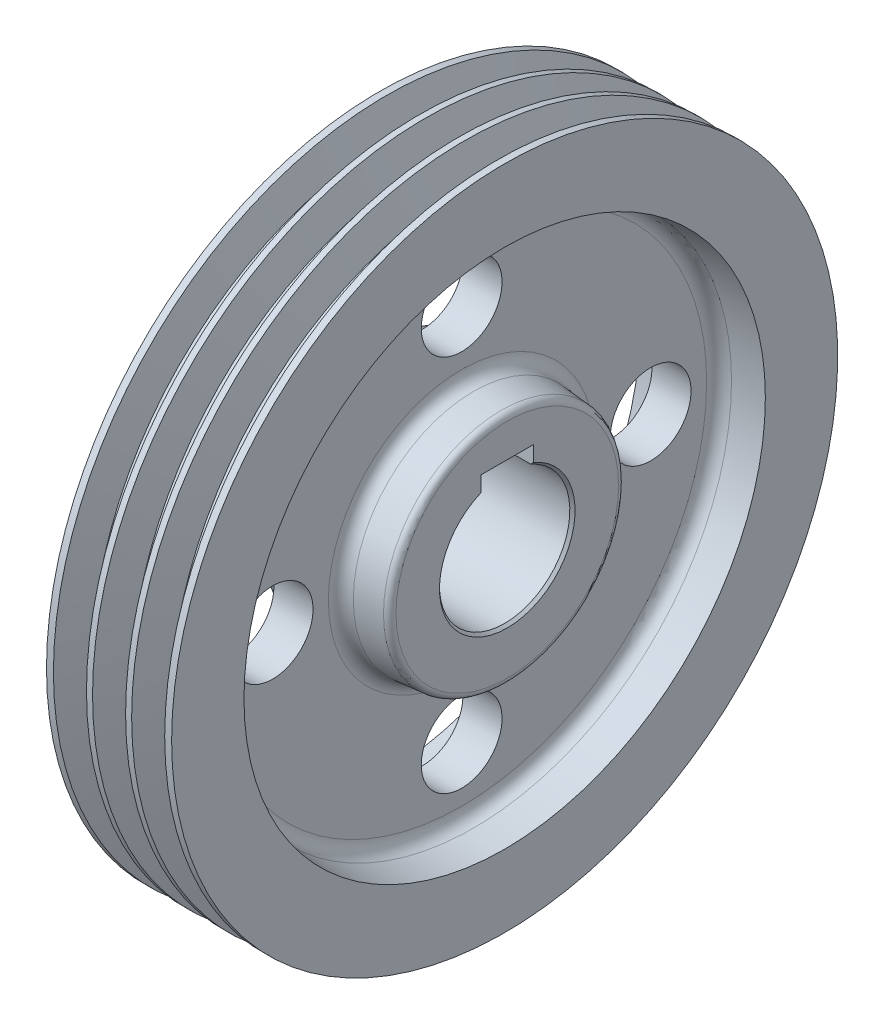
SolidWorks part; units mm, degrees
ref_plane "前视基准面" through (0, 0, 0) normal (0, 0, 1) x (1, 0, 0)
ref_plane "上视基准面" through (0, 0, 0) normal (0, 1, 0) x (1, 0, 0)
ref_plane "右视基准面" through (0, 0, 0) normal (1, 0, 0) x (0, 0, -1)
sketch "草图1" plane through (0, 0, 0) normal (0, 0, 1) x (1, 0, 0)
  line L0 (0, 0) -> (64.8368, 0) construction
  line L1 (-1, 25) -> (-1, 45)
  line L2 (0, 127.75) -> (48, 127.75)
  line L3 (48, 127.75) -> (48, 100)
  line L4 (-1, 45) -> (-30, 45) construction
  line L5 (16.5, 46.5311) -> (16.5, 98.5564)
  line L6 (49, 25) -> (-1, 25)
  line L7 (2.6592, 127.75) -> (6.1599, 116.3) construction
  line L8 (6.1599, 116.3) -> (11.8401, 116.3) construction
  line L9 (11.8401, 116.3) -> (15.3408, 127.75) construction
  line L10 (0, 125) -> (48, 125) construction
  line L11 (9, 116.3) -> (9, 25) construction
  line L12 (44, 100) -> (0, 100) construction
  line L13 (48, 100) -> (79, 100) construction
  line L14 (31.5, 98.5564) -> (31.5, 46.5311)
  line L15 (5, 45) -> (49, 45) construction
  line L16 (24, 25) -> (24, 127.75) construction
  line L17 (49, 45) -> (49, 25)
  line L18 (0, 100) -> (0, 127.75)
  line L19 (16.5, 88) -> (31.5, 88) construction
  line L20 (16.5, 57) -> (31.5, 57) construction
  line L21 (48, 100) -> (48, 88) construction
  line L22 (48, 88) -> (31.5, 88) construction
  line L23 (31.5, 57) -> (49, 57) construction
  line L24 (49, 57) -> (49, 45) construction
  line L25 (31.5, 98.5564) -> (48, 100)
  line L26 (16.5, 98.5564) -> (0, 100)
  line L27 (16.5, 46.5311) -> (-1, 45)
  line L28 (31.5, 46.5311) -> (49, 45)
  point P17 (3.5, 125)
  point P18 (14.5, 125)
  dimension "d2" = 200
  dimension "L" = 50
  dimension "B" = 48
  dimension "d" = 50
  dimension "d1" = 90
  dimension "D3" = 5
  dimension "D4" = 5
  dimension "dd" = 250
  dimension "f" = 9
  dimension "槽轮角" = 34
  dimension "bd" = 11
  dimension "hf" = 8.7
  dimension "ha" = 2.75
  dimension "da" = 255.5
  dimension "S" = 15
  dimension "S2" = 12
revolve "旋转1" add sketch "草图1" angle 360 about L0
sketch "草图2" plane through (0, 0, 0) normal (0, 0, 1) x (1, 0, 0)
  line L0 (11.8401, 116.3) -> (15.3408, 127.75) construction
  line L1 (6.1599, 116.3) -> (11.8401, 116.3) construction
  line L2 (2.6592, 127.75) -> (6.1599, 116.3) construction
  line L3 (11.8401, 116.3) -> (15.3408, 127.75)
  line L4 (6.1599, 116.3) -> (11.8401, 116.3)
  line L5 (2.6592, 127.75) -> (6.1599, 116.3)
  line L6 (2.6592, 127.75) -> (15.3408, 127.75)
  line L7 (0, 0) -> (123, 0) construction
revolve "切除-旋转1" cut sketch "草图2" angle 360 about L7
pattern_linear "轮槽数" count 3 spacing 15 along (1, 0, 0) of "切除-旋转1"
chamfer "倒角1" distance 1 angle 45 2 edges at (-1, 0, 25) (49, 0, 25)
sketch "草图4" plane through (-1, 0, 0) normal (-1, 0, 0) x (0, 0, 1)
  line L1 (-10, 22.9129) -> (10, 22.9129)
  line L2 (-10, 22.9129) -> (-10, 29.9)
  line L3 (-10, 29.9) -> (10, 29.9)
  line L4 (10, 22.9129) -> (10, 29.9)
  circle A0 centre (0, 0) radius 25 construction
  point P6 (5.1, 29.9)
  dimension "键槽高度" = 29.9
  dimension "键槽宽度" = 20
  dimension "t1" = 4.9
extrude "切除-拉伸1" cut sketch "草图4" against normal through all
fillet "圆角1" radius 5 4 edges at (31.5, 0, 98.5564) (16.5, 0, 46.5311) (16.5, 0, 98.5564) (31.5, 0, 46.5311)
fillet "圆角2" radius 2.5 2 edges at (49, 0, 45) (-1, 0, 45)
sketch "草图5" plane through (0, 0, 0) normal (1, 0, 0) x (0, 0, -1)
  line L0 (0, 116.3) -> (0, 25) construction
  circle A0 centre (0, 72.5) radius 15.5
extrude "切除-拉伸2" cut sketch "草图5" along normal through all
pattern_circular "圆孔个数" count 4 over 360 about axis through (0, 0, 0) along (-1, 0, 0) of "切除-拉伸2"
equation "\"B@草图1\" =  ( \"z@轮槽数\" - 1 )  * \"e@轮槽数\" +2 *  \"f@草图1\""
equation "\"键槽高度@草图4\" = \"d@草图1\" / 2 + \"t1@草图4\""
